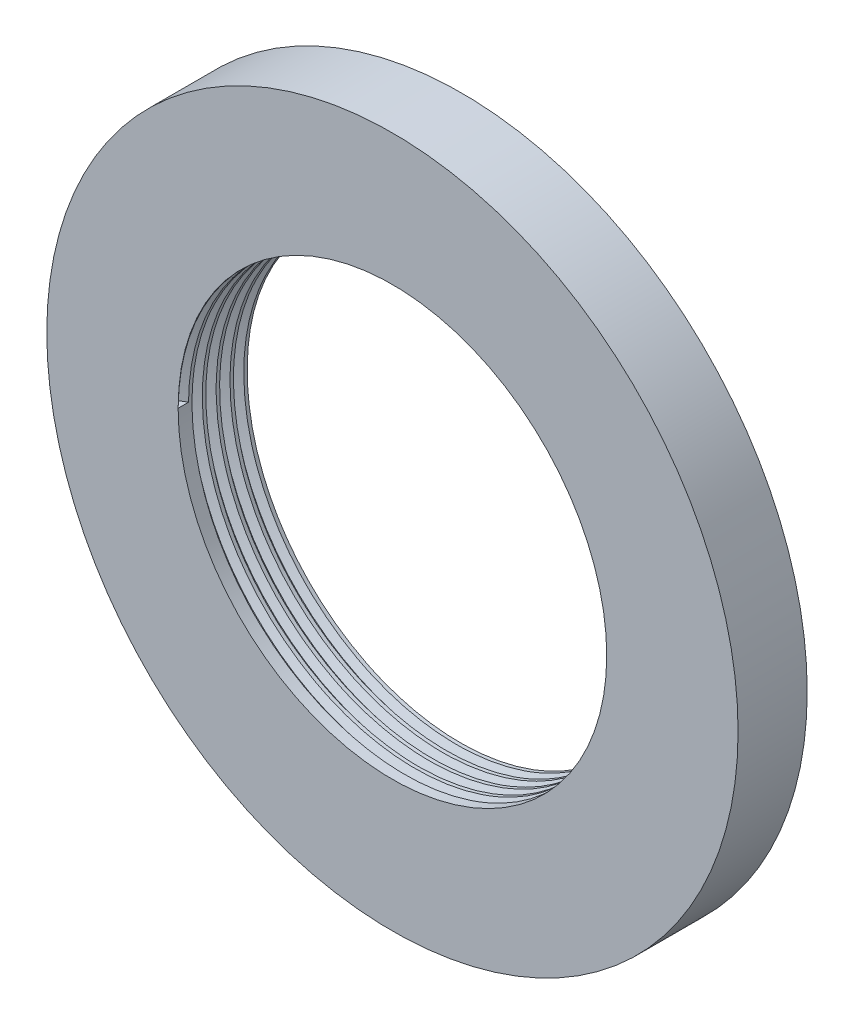
SolidWorks part; units mm, degrees
ref_plane "Front Plane" through (0, 0, 0) normal (0, 0, 1) x (1, 0, 0)
ref_plane "Top Plane" through (0, 0, 0) normal (0, 1, 0) x (1, 0, 0)
ref_plane "Right Plane" through (0, 0, 0) normal (1, 0, 0) x (0, 0, -1)
sketch "Sketch1" plane through (0, 0, 0) normal (0, 0, 1) x (1, 0, 0)
  circle A0 centre (0, 0) radius 15.5
  circle A1 centre (0, 0) radius 25
  dimension "D1" = 50
  dimension "D2" = 31
extrude "Boss-Extrude1" add sketch "Sketch1" along normal blind 5
thread "Thread1" pitch 1 method cut profile "Thread Profile1" start angle 0, offset 0, length 5, pitch 1, diameter 31
ref_plane "Plane1" through (-15.5, 0, 5) normal (0, -1, 0) x (-1, 0, 0)
sketch "Thread Profile1" plane through (-15.5, 0, 5) normal (0, -1, 0) x (-1, 0, 0)
  line L0 (0, 0) -> (0, 1) construction
  line L1 (0, 0) -> (0.5413, 0.3125)
  line L2 (0.5413, 0.3125) -> (0.5413, 0.4375)
  line L3 (0.5413, 0.4375) -> (0, 0.75)
  line L4 (0.5413, 0.375) -> (0, 0.375) construction
  line L11 (0, 0) -> (0, 0.75)
  point P2 (0, 0)
  dimension "Pitch" = 1
  dimension "Profile_Angle" = 60
  dimension "Profile_Land" = 0.125
  dimension "Profile_Height" = 0.5413
